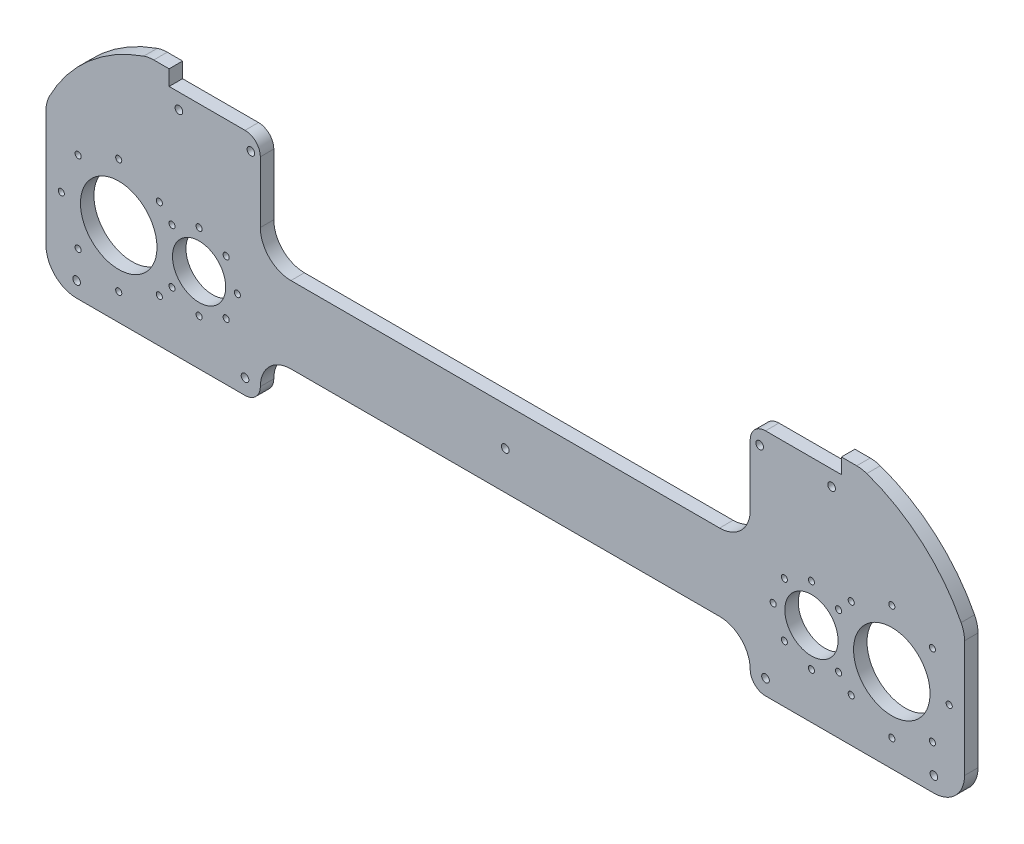
SolidWorks part; units mm, degrees
material "ABS"
ref_plane "Front Plane" through (0, 0, 0) normal (0, 0, 1) x (1, 0, 0)
ref_plane "Top Plane" through (0, 0, 0) normal (0, 1, 0) x (1, 0, 0)
ref_plane "Right Plane" through (0, 0, 0) normal (1, 0, 0) x (0, 0, -1)
sketch "Sketch1" plane through (0, 0, 0) normal (0, 0, 1) x (1, 0, 0)
  line L0 (-145.7836, 66.675) -> (145.7836, 66.675)
  line L1 (-190.5, 26.1817) -> (-190.5, -22.225)
  line L4 (0, 0) -> (0, 100.7987) construction
  line L5 (-177.8, -34.925) -> (177.8, -34.925)
  line L6 (190.5, 26.1817) -> (190.5, -22.225)
  line L7 (-190.5, 34.925) -> (190.5, -34.925) construction
  line L8 (-190.5, -34.925) -> (190.5, 34.925) construction
  arc A0 (177.8, -34.925) -> (190.5, -22.225) centre (177.8, -22.225) ccw
  arc A1 (149.9577, 65.9694) -> (189.0889, 31.9999) centre (127, 0) cw
  circle A2 centre (-127, 0) radius 3.175
  circle A3 centre (127, 0) radius 3.175
  arc A4 (-177.8, -34.925) -> (-190.5, -22.225) centre (-177.8, -22.225) cw
  arc A5 (190.5, 26.1817) -> (189.0889, 31.9999) centre (177.8, 26.1817) ccw
  arc A6 (-149.9577, 65.9694) -> (-189.0889, 31.9999) centre (-127, 0) ccw
  arc A7 (149.9577, 65.9694) -> (145.7836, 66.675) centre (145.7836, 53.975) ccw
  arc A8 (-190.5, 26.1817) -> (-189.0889, 31.9999) centre (-177.8, 26.1817) cw
  arc A9 (-145.7836, 66.675) -> (-149.9577, 65.9694) centre (-145.7836, 53.975) ccw
  point P0 (0, 0)
  point P22 (190.5, 29.0994)
  point P27 (147.8199, 66.675)
  point P30 (-190.5, 29.0994)
  point P33 (-147.8199, 66.675)
  dimension "D3" = 6.35
  dimension "D4" = 6.35
  dimension "D6" = 66.675
  dimension "D7" = 12.7
  dimension "D2" = 381
  dimension "D5" = 12.7
  dimension "D1" = 69.85
  dimension "D8" = 139.7
extrude "Boss-Extrude1" add sketch "Sketch1" along normal mid plane 5.588
sketch "Sketch2" plane through (0, 0, 2.794) normal (0, 0, 1) x (1, 0, 0)
  line L0 (-127, 0) -> (-207.737, 0) construction
  line L1 (127, 0) -> (207.737, 0) construction
  line L4 (0, 0) -> (0, 93.9723) construction
  circle A0 centre (-127, 0) radius 11.049
  circle A1 centre (-160.3375, 0) radius 15.875
  circle A2 centre (-143.4995, 16.838) radius 1.27
  circle A3 centre (-136.525, 0) radius 1.27 [skipped]
  circle A4 centre (-160.3375, 0) radius 23.8125 construction
  circle A5 centre (-127, 0) radius 15.875 construction
  circle A6 centre (-160.3375, 23.8125) radius 1.27
  circle A7 centre (-143.4995, -16.838) radius 1.27
  circle A8 centre (-160.3375, -23.8125) radius 1.27
  circle A9 centre (-177.1755, -16.838) radius 1.27
  circle A10 centre (-184.15, 0) radius 1.27
  circle A11 centre (-177.1755, 16.838) radius 1.27
  circle A12 centre (127, 0) radius 15.875 construction
  circle A13 centre (160.3375, 0) radius 23.8125 construction
  circle A14 centre (-127, 15.875) radius 1.27
  circle A15 centre (-115.7747, 11.2253) radius 1.27
  circle A16 centre (-111.125, 0) radius 1.27
  circle A17 centre (-115.7747, -11.2253) radius 1.27
  circle A18 centre (-127, -15.875) radius 1.27
  circle A19 centre (-138.2253, -11.2253) radius 1.27
  circle A20 centre (138.2253, 11.2253) radius 1.27
  circle A21 centre (-138.2253, 11.2253) radius 1.27
  circle A22 centre (-142.875, 0) radius 1.27 [skipped]
  circle A23 centre (138.2253, -11.2253) radius 1.27
  circle A24 centre (127, -15.875) radius 1.27
  circle A25 centre (115.7747, -11.2253) radius 1.27
  circle A26 centre (111.125, 0) radius 1.27
  circle A27 centre (115.7747, 11.2253) radius 1.27
  circle A28 centre (127, 15.875) radius 1.27
  circle A29 centre (177.1755, 16.838) radius 1.27
  circle A30 centre (184.15, 0) radius 1.27
  circle A31 centre (177.1755, -16.838) radius 1.27
  circle A32 centre (160.3375, -23.8125) radius 1.27
  circle A33 centre (143.4995, -16.838) radius 1.27
  circle A34 centre (160.3375, 23.8125) radius 1.27
  circle A35 centre (143.4995, 16.838) radius 1.27
  circle A36 centre (160.3375, 0) radius 15.875
  circle A37 centre (127, 0) radius 11.049
  dimension "D2" = 33.3375
  dimension "D3" = 31.75
  dimension "D4" = 31.75
  dimension "D5" = 47.625
  dimension "D6" = 2.54
  dimension "D1" = 22.098
  dimension "D8" = 2.54
  dimension "D7" = 8
  dimension "D9" = 8
extrude "Cut-Extrude1" cut sketch "Sketch2" against normal through all
sketch "Sketch5" plane through (0, 0, 2.794) normal (0, 0, 1) x (1, 0, 0)
  line L0 (145.7836, 66.675) -> (-145.7836, 66.675) construction
  line L1 (-88.9, 15.875) -> (88.9, 15.875)
  line L2 (-101.6, 28.575) -> (-101.6, 66.675)
  line L3 (-101.6, 66.675) -> (101.6, 66.675)
  line L4 (101.6, 28.575) -> (101.6, 66.675)
  line L5 (-101.6, 15.875) -> (101.6, 66.675) construction
  line L6 (-101.6, 66.675) -> (101.6, 15.875) construction
  line L7 (0, 0) -> (0, 128.2224) construction
  arc A0 (101.6, 28.575) -> (88.9, 15.875) centre (88.9, 28.575) cw
  arc A1 (-88.9, 15.875) -> (-101.6, 28.575) centre (-88.9, 28.575) cw
  point P0 (0, 41.275)
  dimension "D3" = 12.7
  dimension "D1" = 50.8
  dimension "D2" = 203.2
extrude "ITC_Cutout" cut sketch "Sketch5" against normal through all
sketch "Sketch6" plane through (0, 0, 2.794) normal (0, 0, 1) x (1, 0, 0)
  line L0 (-101.6, 66.675) -> (-145.7836, 66.675) construction
  line L1 (-71.9103, 66.675) -> (-139.4336, 66.675)
  line L2 (-71.9103, 66.675) -> (-71.9103, 60.325)
  line L3 (-71.9103, 60.325) -> (-139.4336, 60.325)
  line L4 (-139.4336, 66.675) -> (-139.4336, 60.325)
  line L5 (0, 0) -> (0, 132.6418) construction
  line L6 (139.4336, 66.675) -> (139.4336, 60.325)
  line L7 (71.9103, 60.325) -> (139.4336, 60.325)
  line L8 (71.9103, 66.675) -> (71.9103, 60.325)
  line L9 (71.9103, 66.675) -> (139.4336, 66.675)
  dimension "D1" = 6.35
  dimension "D2" = 6.35
extrude "Cut-Extrude3" cut sketch "Sketch6" against normal through all
fillet "Fillet1" radius 6.35 2 edges at (101.6, 60.325, 0) (-101.6, 60.325, 0)
sketch "Sketch7" plane through (0, 0, 2.794) normal (0, 0, 1) x (1, 0, 0)
  line L0 (0, 38.9819) -> (0, -79.3414) construction
  line L1 (-177.8, -34.925) -> (177.8, -34.925) construction
  line L2 (-88.9, -15.875) -> (88.9, -15.875)
  line L3 (-101.6, -28.575) -> (-101.6, -34.925)
  line L4 (-101.6, -34.925) -> (101.6, -34.925)
  line L5 (101.6, -28.575) -> (101.6, -34.925)
  line L6 (-101.6, -15.875) -> (101.6, -34.925) construction
  line L7 (-101.6, -34.925) -> (101.6, -15.875) construction
  line L8 (-101.6, 53.975) -> (-101.6, 28.575) construction
  arc A0 (101.6, -28.575) -> (88.9, -15.875) centre (88.9, -28.575) ccw
  arc A1 (-88.9, -15.875) -> (-101.6, -28.575) centre (-88.9, -28.575) ccw
  point P3 (0, -25.4)
  dimension "D2" = 12.7
  dimension "D1" = 19.05
extrude "Cut-Extrude4" cut sketch "Sketch7" against normal through all
fillet "Fillet2" radius 6.35 2 edges at (101.6, -34.925, 0) (-101.6, -34.925, 0)
sketch "Sketch8" plane through (0, 0, 2.794) normal (0, 0, 1) x (1, 0, 0)
  line L0 (-139.4336, 60.325) -> (-107.95, 60.325) construction
  line L1 (-139.4336, 66.675) -> (-139.4336, 60.325) construction
  line L2 (0, 0) -> (0, 74.8203) construction
  circle A0 centre (-135.3696, 53.975) radius 1.5875
  circle A1 centre (-105.5246, 53.975) radius 1.5875
  circle A2 centre (105.5246, 53.975) radius 1.5875
  circle A3 centre (135.3696, 53.975) radius 1.5875
  dimension "D1" = 3.175
  dimension "D3" = 3.175
  dimension "D2" = 6.35
  dimension "D4" = 29.845
  dimension "D5" = 4.064
extrude "Cut-Extrude5" cut sketch "Sketch8" against normal through all
sketch "Sketch10" plane through (0, 0, 2.794) normal (0, 0, 1) x (1, 0, 0)
  line L0 (0, 50.0636) -> (0, -61.6077) construction
  line L1 (-177.8, -34.925) -> (-107.95, -34.925) construction
  circle A0 centre (-177.8, -28.575) radius 1.5875
  circle A1 centre (-107.95, -28.575) radius 1.5875
  circle A2 centre (107.95, -28.575) radius 1.5875
  circle A3 centre (177.8, -28.575) radius 1.5875
  circle A4 centre (0, 0) radius 1.5875
  dimension "D1" = 3.175
  dimension "D4" = 3.175
  dimension "D6" = 3.175
  dimension "D2" = 6.35
  dimension "D3" = 177.8
  dimension "D5" = 107.95
extrude "Cut-Extrude6" cut sketch "Sketch10" against normal through all
equation "\"D3@Sketch8\" = \"D1@Sketch8\""
